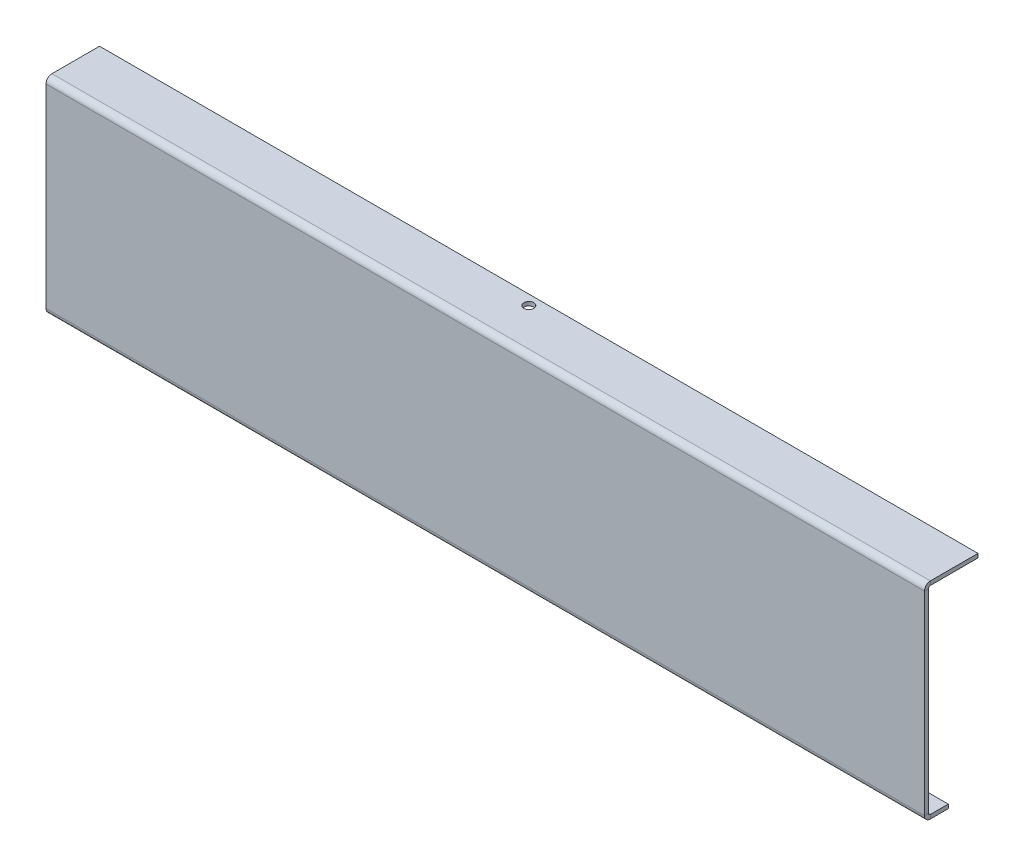
SolidWorks part; units mm, degrees
note: The reader was unsure of these and kept them because the rebuilt part matched: flange length of "Edge-Flange1", "Edge-Flange2".
material "Chrome Stainless Steel"
ref_plane "Front Plane" through (0, 0, 0) normal (0, 0, 1) x (1, 0, 0)
ref_plane "Top Plane" through (0, 0, 0) normal (0, 1, 0) x (1, 0, 0)
ref_plane "Right Plane" through (0, 0, 0) normal (1, 0, 0) x (0, 0, -1)
sketch "Sketch1" plane through (0, 0, 0) normal (0, 0, 1) x (1, 0, 0)
  line L1 (-221.5, 50) -> (221.5, 50)
  line L2 (-221.5, 50) -> (-221.5, -50)
  line L3 (-221.5, -50) -> (221.5, -50)
  line L4 (221.5, 50) -> (221.5, -50)
  line L5 (-221.5, 50) -> (221.5, -50) construction
  line L6 (-221.5, -50) -> (221.5, 50) construction
  point P0 (0, 0)
  dimension "D1" = 443
  dimension "D2" = 100
base flange "Base-Flange1" sketch "Sketch1" thickness 2 reverse thickness direction no parameters "D1"=6.35
edge flange "Edge-Flange1" sketch "Sketch8" flange angle 90 flange length 25 flange position material outside bend radius 1 thickness 2 relief rectangular parameters "D6"=10
sketch "Sketch8" plane through (0, 50, -2) normal (0, -1, 0) x (-1, 0, 0)
  line L2 (-221.5, 0) -> (-221.5, 25)
  line L3 (-221.5, 25) -> (221.5, 25)
  line L4 (221.5, 25) -> (221.5, 0)
  line L5 (221.5, 0) -> (-221.5, 0) construction
  line L6 (221.5, 0) -> (-221.5, 0)
bend "EdgeBend1" bend radius 1 bend angle 90 parameters "D5"=1
edge flange "Edge-Flange2" sketch "Sketch11" flange angle 90 flange length 10 flange position material outside bend radius 1 thickness 2 relief rectangular parameters "D6"=10
sketch "Sketch11" plane through (0, -50, -2) normal (0, 1, 0) x (1, 0, 0)
  line L2 (-221.5, 0) -> (-221.5, 10)
  line L3 (-221.5, 10) -> (221.5, 10)
  line L4 (221.5, 10) -> (221.5, 0)
  line L5 (221.5, 0) -> (-221.5, 0) construction
  line L6 (221.5, 0) -> (-221.5, 0)
bend "EdgeBend2" bend radius 1 bend angle 90 parameters "D5"=2
sketch "Sketch13" plane through (0, 52, 0) normal (0, 1, 0) x (1, 0, 0)
  line L0 (0, 0) -> (0, 27) construction
  line L1 (-221.5, 27) -> (221.5, 27) construction
  line L7 (-221.5, 27) -> (-221.5, 3)
  line L8 (-221.5, 3) -> (221.5, 3)
  line L9 (221.5, 3) -> (221.5, 27)
  line L10 (221.5, 27) -> (-221.5, 27)
  line L11 (-221.5, 27) -> (-221.5, 3)
  line L12 (-221.5, 3) -> (221.5, 3)
  line L13 (221.5, 3) -> (221.5, 27)
  line L14 (221.5, 27) -> (-221.5, 27)
  circle A0 centre (0, 22) radius 2.5
  dimension "D1" = 5
  dimension "D2" = 0
  dimension "D3" = 19
extrude "Cut-Extrude2" cut sketch "Sketch13" against normal blind 10 contours L0 A0 | A0 L0
sketch "Bend-Lines1" plane through (0, 0, 0) normal (0, 1, 0) x (1, 0, 0)
sketch "Bounding-Box1" plane through (0, 0, 0) normal (0, 1, 0) x (1, 0, 0)
sheet metal parameters "Sheet-Metal1" thickness 2 parameters "D1"=6.35
flat pattern "Flat-Pattern1" [suppressed]
sketch "Bend-Lines2" plane through (0, 0, 0) normal (0, 1, 0) x (1, 0, 0)
sketch "Bounding-Box2" [suppressed] plane through (0, 0, 0) normal (0, 1, 0) x (1, 0, 0)
sheet metal parameters "Sheet-Metal2" thickness 2 parameters "D1"=6.35
flat pattern "Flat-Pattern1" [suppressed]
sketch "Bend-Lines2" plane through (0, 0, 0) normal (0, 1, 0) x (1, 0, 0)
sketch "Bounding-Box2" [suppressed] plane through (0, 0, 0) normal (0, 1, 0) x (1, 0, 0)
bend of the flat pattern "Flatten-<EdgeBend1>1"
sheet metal parameters "Sheet-Metal3" thickness 2 parameters "D1"=6.35
flat pattern "Flat-Pattern1" [suppressed]
sketch "Bend-Lines2" plane through (0, 0, 0) normal (0, 1, 0) x (1, 0, 0)
sketch "Bounding-Box2" [suppressed] plane through (0, 0, 0) normal (0, 1, 0) x (1, 0, 0)
bend of the flat pattern "Flatten-<EdgeBend1>1"
bend of the flat pattern "Flatten-<EdgeBend2>1"
sheet metal parameters "Sheet-Metal4" thickness 2 parameters "D1"=6.35
flat pattern "Flat-Pattern1" [suppressed]
sketch "Bend-Lines2" plane through (0, 0, 0) normal (0, 1, 0) x (1, 0, 0)
sketch "Bounding-Box2" [suppressed] plane through (0, 0, 0) normal (0, 1, 0) x (1, 0, 0)
bend of the flat pattern "Flatten-<EdgeBend1>1"
bend of the flat pattern "Flatten-<EdgeBend2>1"
